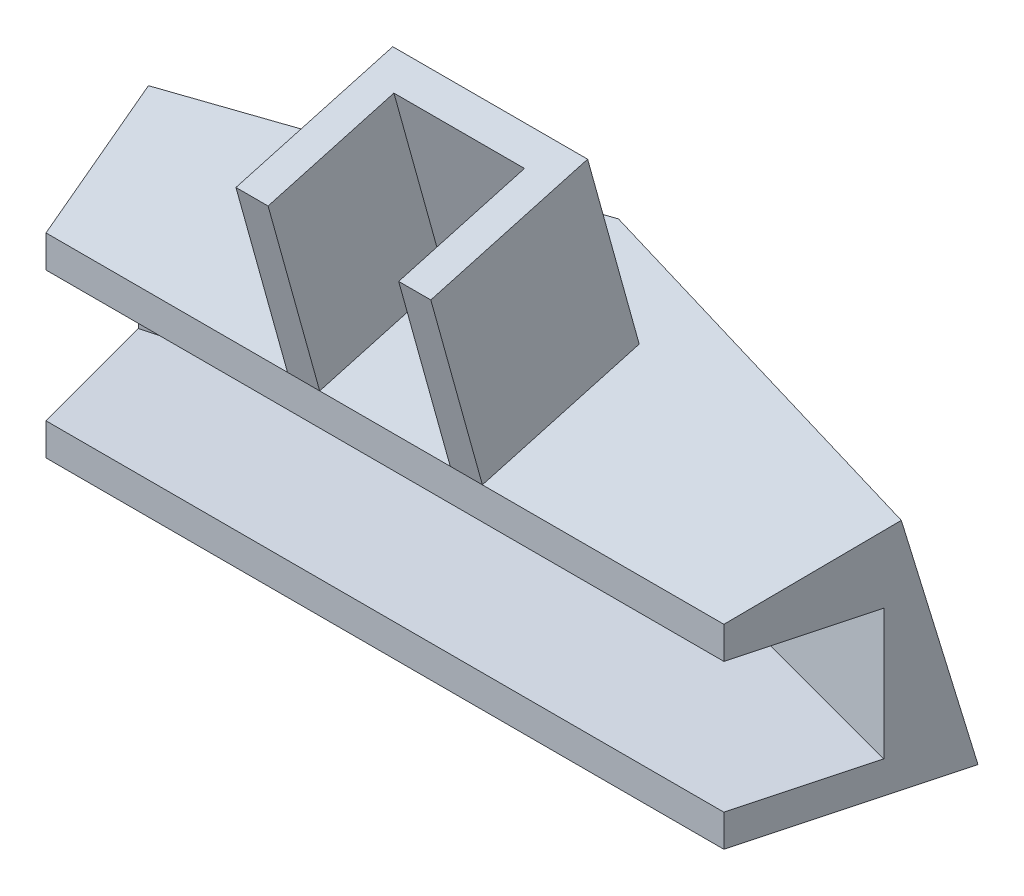
SolidWorks part; units mm, degrees
ref_plane "Front Plane" through (0, 0, 0) normal (0, 0, 1) x (1, 0, 0)
ref_plane "Top Plane" through (0, 0, 0) normal (0, 1, 0) x (1, 0, 0)
ref_plane "Right Plane" through (0, 0, 0) normal (1, 0, 0) x (0, 0, -1)
sketch "Sketch4" plane through (0, 0, 0) normal (0, 1, 0) x (1, 0, 0)
  line L0 (0, 0) -> (0, -14.1213) construction
  line L1 (-52.7015, -14.1213) -> (52.7015, -14.1213) construction
  line L2 (0, 0) -> (-52.7015, -14.1213) construction
  line L3 (0, 0) -> (52.7015, -14.1213) construction
  line L4 (52.7015, -14.1213) -> (57.9555, 5.487) construction
  line L5 (-52.7015, -14.1213) -> (-57.9555, 5.487) construction
  line L6 (0, 0) -> (0, 21.0161) construction
  line L7 (57.9555, 5.487) -> (0, 21.0161) construction
  line L8 (-57.9555, 5.487) -> (0, 21.0161) construction
  line L9 (-57.9555, 5.487) -> (-63.1319, 24.8055) construction
  line L10 (57.9555, 5.487) -> (63.1319, 24.8055) construction
  line L11 (-63.1319, 24.8055) -> (0, 41.7216) construction
  line L12 (0, 41.7216) -> (63.1319, 24.8055) construction
  line L13 (0, 21.0161) -> (0, 41.7216)
  arc A0 (-15.1096, -4.0486) -> (15.1096, -4.0486) centre (0, 0) ccw construction
sketch "Sketch8" plane through (0, 0, 0) normal (0, 1, 0) x (1, 0, 0)
  line L0 (-63.1319, 24.8055) -> (-52.7015, -14.1213)
  line L1 (-52.7015, -14.1213) -> (52.7015, -14.1213) construction
  line L2 (52.7015, -14.1213) -> (63.1319, 24.8055) construction
  line L3 (63.1319, 24.8055) -> (0, 41.7216) construction
  line L4 (0, 41.7216) -> (-63.1319, 24.8055)
  line L5 (0, 41.7216) -> (0, -14.1213)
  line L6 (0, -14.1213) -> (-52.7015, -14.1213)
extrude "Boss-Extrude5" add sketch "Sketch8" along normal blind 5
sketch "Sketch9" plane through (0, 5, 0) normal (0, 1, 0) x (1, 0, 0)
  line L0 (-63.1319, 24.8055) -> (-57.9555, 5.487)
  line L1 (-57.9555, 5.487) -> (0, 21.0161)
  line L2 (-63.1319, 24.8055) -> (0, 41.7216)
  line L6 (0, 41.7216) -> (0, 21.0161)
extrude "Boss-Extrude6" add sketch "Sketch9" along normal blind 20.3
sketch "Sketch10" plane through (0, 25.3, 0) normal (0, 1, 0) x (1, 0, 0)
  line L7 (0, 41.7216) -> (0, -14.1213)
  line L8 (0, -14.1213) -> (-52.7015, -14.1213)
  line L9 (-52.7015, -14.1213) -> (-63.1319, 24.8055)
  line L10 (-63.1319, 24.8055) -> (0, 41.7216)
extrude "Boss-Extrude7" add sketch "Sketch10" along normal blind 20
sketch "Sketch19" plane through (-52.7015, 0, 14.1213) normal (-0.9659, 0, 0.2588) x (0.2588, 0, 0.9659)
  line L0 (-20.3, 25.3) -> (-25.1296, 26.5941) construction
  line L1 (-32.2555, 0) -> (-20.1174, 45.3)
  line L2 (-40.3, 0) -> (0, 0) construction
  line L3 (-40.3, 45.3) -> (0, 45.3) construction
  line L4 (-20.1174, 45.3) -> (-40.3, 45.3)
  line L5 (-40.3, 45.3) -> (-40.3, 0)
  line L6 (-40.3, 0) -> (-32.2555, 0)
  line L7 (-20.1174, 45.3) -> (-20.1174, 0) construction
  arc A0 (-17.2193, 56.116) -> (-20.1174, 34.1025) centre (-20.1174, 45.3) ccw construction
extrude "Cut-Extrude1" cut sketch "Sketch19" against normal through all
sketch "Sketch22" plane through (0, 0, 0) normal (1, 0, 0) x (0, 0, -1)
  line L0 (-14.1213, 25.3) -> (-14.1213, 30.3) construction
  line L1 (-14.1213, 45.3) -> (-14.1213, 25.3) construction
  line L2 (-14.1213, 30.3) -> (22.1936, 40.3738)
  line L3 (33.3933, 0) -> (20.8271, 45.3) construction
  line L4 (-14.1213, 30.3) -> (-14.1213, 45.3)
  line L5 (-14.1213, 45.3) -> (20.8271, 45.3)
  line L6 (20.8271, 45.3) -> (22.1936, 40.3738)
extrude "Cut-Extrude3" cut sketch "Sketch22" against normal through all
sketch "Sketch23" plane through (0, 31.7723, 8.8137) normal (0, 0.9636, 0.2673) x (1, 0, 0)
  line L0 (-10.15, -5.5081) -> (-15.15, -5.5081)
  line L1 (-52.7015, -5.5081) -> (0, -5.5081) construction
  line L2 (-10.15, -5.5081) -> (-10.15, 14.7919)
  line L3 (-10.15, 14.7919) -> (0, 14.7919)
  line L4 (0, -5.5081) -> (0, 32.1782) construction
  line L5 (-15.15, -5.5081) -> (-15.15, 19.7919)
  line L6 (-15.15, 19.7919) -> (0, 19.7919)
  line L7 (0, 19.7919) -> (0, 14.7919)
extrude "Boss-Extrude9" add sketch "Sketch23" along normal blind 30
mirror "Mirror1" about plane through (0, 5, -41.7216) normal (-1, 0, 0) of "Boss-Extrude9", "Cut-Extrude3", "Cut-Extrude1", "Boss-Extrude7", "Boss-Extrude6", "Boss-Extrude5"
